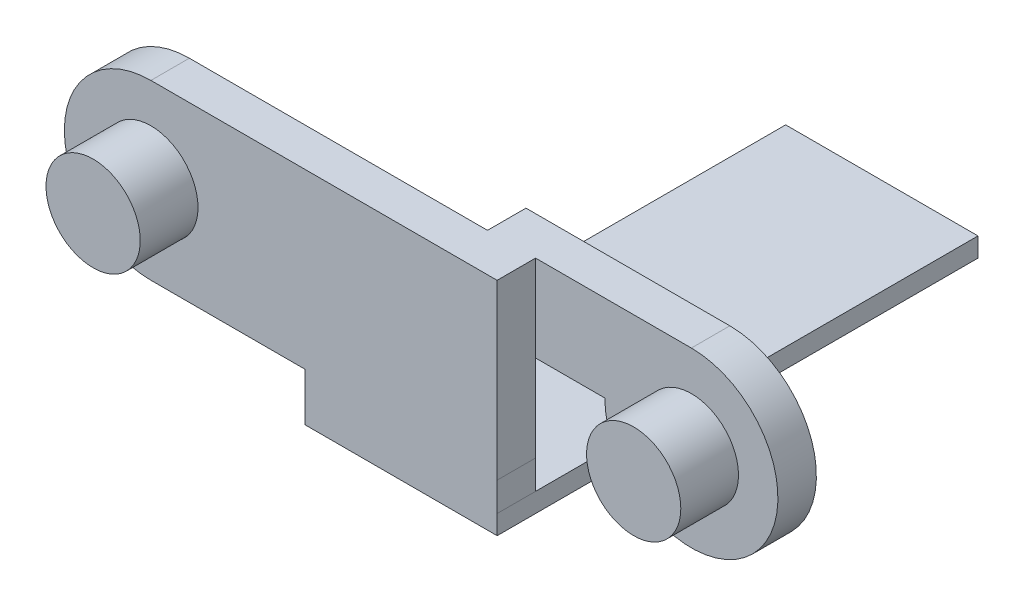
SolidWorks part; units mm, degrees
ref_plane "前视基准面" through (0, 0, 0) normal (0, 0, 1) x (1, 0, 0)
ref_plane "上视基准面" through (0, 0, 0) normal (0, 1, 0) x (1, 0, 0)
ref_plane "右视基准面" through (0, 0, 0) normal (1, 0, 0) x (0, 0, -1)
sketch "草图1" plane through (0, 0, 0) normal (0, 0, 1) x (1, 0, 0)
  line L0 (-70.4586, -12.3103) -> (-78.4607, -12.3103)
  line L18 (-56.8607, -7.8103) -> (-60.4607, -7.8103)
  line L24 (-52.3607, -3.3103) -> (-60.4607, -3.3103)
  line L26 (-60.4607, -3.3103) -> (-78.4607, -3.3103)
  line L27 (-60.4607, -3.3103) -> (-60.4607, -12.3103)
  line L36 (-70.4586, -13.8103) -> (-70.4586, -12.3103)
  line L37 (-60.4586, -13.8103) -> (-60.4607, -12.3103)
  line L39 (-70.4586, -13.8103) -> (-60.4586, -13.8103)
  line L40 (-70.4586, -13.8103) -> (-70.4586, -14.8103)
  line L41 (-70.4586, -14.8103) -> (-60.4586, -14.8103)
  line L42 (-60.4586, -13.8103) -> (-60.4586, -14.8103)
  circle A0 centre (-52.3607, -7.8103) radius 2.45
  arc A3 (-56.8607, -7.8103) -> (-52.3607, -3.3103) centre (-52.3607, -7.8103) ccw
  arc A4 (-78.4607, -3.3103) -> (-78.4607, -12.3103) centre (-78.4607, -7.8103) ccw
  circle A5 centre (-78.4607, -7.8103) radius 2.45
extrude "凸台-拉伸2" add sketch "草图1" against normal blind 2 contours L18 A3 L24 A0 region at (-56.4107, -3.4652, 0)
extrude "凸台-拉伸3" add sketch "草图1<5>" along normal blind 2 separate body contours L26 A4 L0 L36 L37 L27 A5 region at (-70.0782, -8.2249, 0)
sketch "草图1<5>" plane through (0, 0, 0) normal (0, 0, 1) x (1, 0, 0) same geometry as "草图1"
sketch "草图5" plane through (0, 0, -2) normal (0, 0, -1) x (-1, 0, 0)
sketch "草图8" plane through (0, 0, 0) normal (0, 0, 1) x (1, 0, 0)
  circle A0 centre (-52.3607, -7.8103) radius 2.45
extrude "凸台-拉伸5" add sketch "草图8" along normal blind 3 separate body
sketch "草图10" plane through (0, 0, 0) normal (0, 0, 1) x (1, 0, 0)
  circle A0 centre (-52.4388, -7.7957) radius 2.5295
extrude "凸台-拉伸6" add sketch "草图10" against normal blind 2
sketch "草图11" plane through (0, 0, 0) normal (0, 0, -1) x (-1, 0, 0)
  line L1 (60.4607, -3.3103) -> (62.9607, -3.3103)
  line L2 (60.4607, -3.3103) -> (60.4607, -7.8103)
  line L3 (60.4607, -7.8103) -> (62.9607, -7.8103)
  line L4 (62.9607, -3.3103) -> (62.9607, -7.8103)
extrude "凸台-拉伸7" add sketch "草图11" along normal blind 2
extrude "凸台-拉伸8" add sketch "草图1<7>" against normal blind 23 separate body contours L42 L40 L41 region at (-65.4586, -14.3103, 0)
sketch "草图1<7>" plane through (0, 0, 0) normal (0, 0, 1) x (1, 0, 0) same geometry as "草图1"
sketch "草图13" plane through (0, 0, 0) normal (0, 0, 1) x (1, 0, 0)
  line L0 (-70.4586, -14.8103) -> (-60.4586, -14.8103) construction
  line L1 (-70.4586, -13.8103) -> (-60.4586, -13.8103)
  line L2 (-70.4586, -13.8103) -> (-70.4586, -14.8103)
  line L3 (-70.4586, -14.8103) -> (-60.4586, -14.8103)
  line L4 (-60.4586, -13.8103) -> (-60.4586, -14.8103)
extrude "凸台-拉伸9" add sketch "草图13" along normal blind 2
sketch "草图15" plane through (0, 0, 0) normal (0, 0, -1) x (-1, 0, 0)
  circle A0 centre (80.8921, -7.0402) radius 0.1004
sketch "草图18" plane through (0, 0, 0) normal (0, 0, -1) x (-1, 0, 0)
  circle A0 centre (80.6027, -6.6042) radius 0.0082
  circle A1 centre (76.7939, -9.5933) radius 0.0092
sketch "草图19" plane through (0, 0, 0) normal (0, 0, -1) x (-1, 0, 0)
sketch "草图21" plane through (0, 0, 0) normal (0, 0, -1) x (-1, 0, 0)
  circle A0 centre (78.4652, -7.8016) radius 2.45
extrude "凸台-拉伸10" add sketch "草图21" against normal blind 5
